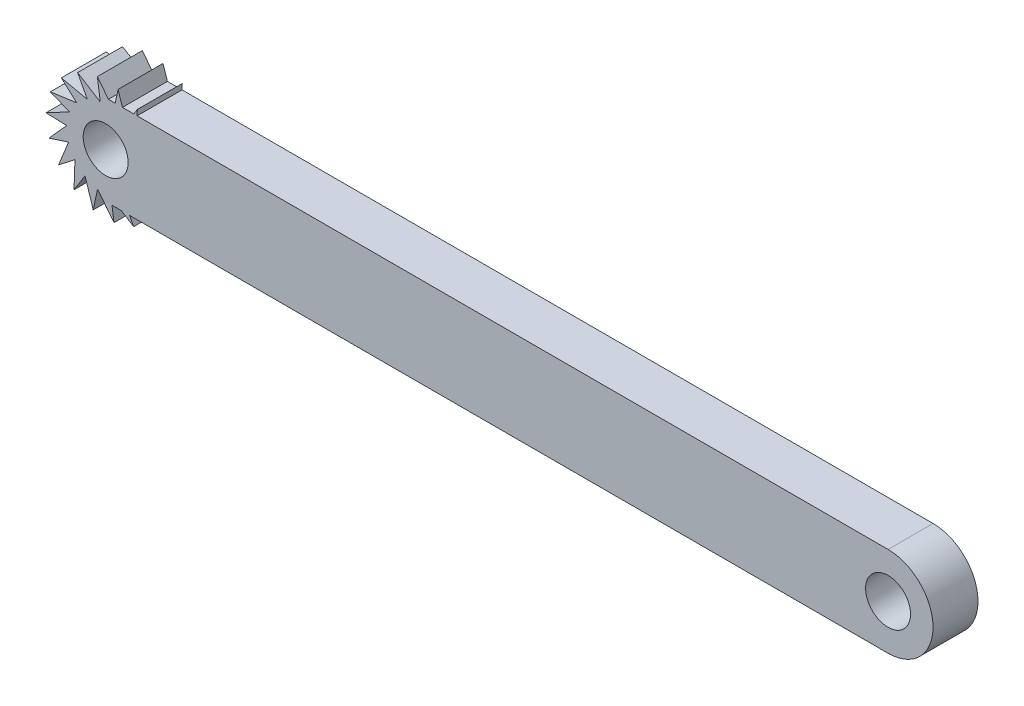
SolidWorks part; units mm, degrees
material "1060 Alloy"
ref_plane "Front Plane" through (0, 0, 0) normal (0, 0, 1) x (1, 0, 0)
ref_plane "Top Plane" through (0, 0, 0) normal (0, 1, 0) x (1, 0, 0)
ref_plane "Right Plane" through (0, 0, 0) normal (1, 0, 0) x (0, 0, -1)
sketch "Sketch1" plane through (0, 0, 0) normal (0, 0, 1) x (1, 0, 0)
  line L0 (-71.3706, 0) -> (276.6294, 0) construction
  line L1 (-71.3706, 20) -> (276.6294, 20)
  line L2 (-71.3706, -20) -> (276.6294, -20)
  arc A0 (-71.3706, 20) -> (-71.3706, -20) centre (-71.3706, 0) ccw
  arc A1 (276.6294, -20) -> (276.6294, 20) centre (276.6294, 0) ccw
  circle A2 centre (-71.3706, 0) radius 10
  circle A3 centre (276.6294, 0) radius 10
  point P3 (102.6294, 0)
extrude "Boss-Extrude1" add sketch "Sketch1" along normal blind 20
sketch "Sketch2" plane through (0, 0, 0) normal (0, 0, -1) x (-1, 0, 0)
  line L0 (71.3706, -20) -> (71.3706, -25)
  line L1 (62.5643, -17.9569) -> (58.8706, -21.6506)
  arc A0 (62.5643, -17.9569) -> (71.3706, -20) centre (71.3706, 0) ccw
  arc A1 (58.8706, -21.6506) -> (71.3706, -25) centre (71.3706, 0) ccw
  arc A2 (71.3706, -20) -> (71.3706, 20) centre (71.3706, 0) ccw construction
  dimension "D1" = 50
  dimension "D2" = 45
extrude "Boss-Extrude2" add sketch "Sketch2" along normal blind 20
ref_plane "Plane1" through (0, 0, 15) normal (0, 0, 1) x (1, 0, 0)
sketch "Sketch6" plane through (0, 0, 15) normal (0, 0, 1) x (1, 0, 0)
  line L0 (-65.8481, 25.9708) -> (-62.1857, 14.6962)
  line L1 (-67.766, 16.9513) -> (-65.8481, 25.9708)
  line L2 (-75.0637, 26.2934) -> (-67.766, 16.9513)
  line L3 (-62.1857, 14.6962) -> (-57.2986, 22.5158)
  line L4 (-57.2986, 22.5158) -> (-57.7133, 10.6685)
  line L5 (-57.7133, 10.6685) -> (-50.4464, 16.3451)
  line L6 (-50.4464, 16.3451) -> (-54.8881, 5.354)
  line L7 (-54.8881, 5.354) -> (-46.1179, 8.2028)
  line L8 (-46.1179, 8.2028) -> (-54.0509, -0.6062)
  line L9 (-54.0509, -0.6062) -> (-44.8353, -0.9288)
  line L10 (-44.8353, -0.9288) -> (-55.3027, -6.4933)
  line L11 (-55.3027, -6.4933) -> (-46.7532, -9.9483)
  line L12 (-46.7532, -9.9483) -> (-58.4926, -11.5972)
  line L13 (-58.4926, -11.5972) -> (-51.6404, -17.768)
  line L14 (-51.6404, -17.768) -> (-63.2357, -15.3024)
  line L15 (-63.2357, -15.3024) -> (-58.9073, -23.4446)
  line L16 (-58.9073, -23.4446) -> (-68.96, -17.1618)
  line L17 (-68.96, -17.1618) -> (-67.6774, -26.2934)
  line L18 (-67.6774, -26.2934) -> (-74.9751, -16.9513)
  line L19 (-74.9751, -16.9513) -> (-76.893, -25.9708)
  line L20 (-76.893, -25.9708) -> (-80.5554, -14.6962)
  line L21 (-80.5554, -14.6962) -> (-85.4425, -22.5158)
  line L22 (-85.4425, -22.5158) -> (-85.0278, -10.6685)
  line L23 (-85.0278, -10.6685) -> (-92.2947, -16.3451)
  line L24 (-92.2947, -16.3451) -> (-87.853, -5.354)
  line L25 (-87.853, -5.354) -> (-96.6232, -8.2028)
  line L26 (-96.6232, -8.2028) -> (-88.6902, 0.6062)
  line L27 (-88.6902, 0.6062) -> (-97.9058, 0.9288)
  line L28 (-97.9058, 0.9288) -> (-87.4384, 6.4933)
  line L29 (-87.4384, 6.4933) -> (-95.9879, 9.9483)
  line L30 (-95.9879, 9.9483) -> (-84.2485, 11.5972)
  line L31 (-84.2485, 11.5972) -> (-91.1008, 17.768)
  line L32 (-91.1008, 17.768) -> (-79.5054, 15.3024)
  line L33 (-79.5054, 15.3024) -> (-83.8339, 23.4446)
  line L34 (-83.8339, 23.4446) -> (-73.7811, 17.1618)
  line L35 (-73.7811, 17.1618) -> (-75.0637, 26.2934)
  circle A0 centre (-71.3706, 0) radius 26.5515 construction
  circle A1 centre (-71.3706, 0) radius 17.3303 construction
  circle A2 centre (-71.3706, 0) radius 10
  point P61 (-71.3706, 0)
  dimension "D1" = 50
  dimension "D2" = 18
extrude "Boss-Extrude3" add sketch "Sketch6" against normal blind 15 and the other way blind 10 contours L30 L31 L32 L33 L34 L35 L2 L1 L0 L3 L4 L5 L6 L7 L8 L9 L10 L11 L12 L13 L14 L15 L16 L17 L18 L19 L20 L21 L22 L23 L24 L25 L26 L27 L28 L29
sketch "Sketch8" plane through (0, 0, 0) normal (0, 0, -1) x (-1, 0, 0)
  line L36 (88.6902, 0.6062) -> (97.9058, 0.9288)
  line L37 (97.9058, 0.9288) -> (87.4384, 6.4933)
  line L38 (87.4384, 6.4933) -> (95.9879, 9.9483)
  line L39 (95.9879, 9.9483) -> (84.2485, 11.5972)
  line L40 (84.2485, 11.5972) -> (91.1008, 17.768)
  line L41 (91.1008, 17.768) -> (79.5054, 15.3024)
  line L42 (79.5054, 15.3024) -> (83.8339, 23.4446)
  line L43 (83.8339, 23.4446) -> (73.7811, 17.1618)
  line L44 (73.7811, 17.1618) -> (75.0637, 26.2934)
  line L45 (75.0637, 26.2934) -> (67.766, 16.9513)
  line L46 (67.766, 16.9513) -> (65.8481, 25.9708)
  line L47 (65.8481, 25.9708) -> (62.1857, 14.6962)
  line L48 (62.1857, 14.6962) -> (57.2986, 22.5158)
  line L49 (57.2986, 22.5158) -> (57.7133, 10.6685)
  line L50 (57.7133, 10.6685) -> (50.4464, 16.3451)
  line L51 (50.4464, 16.3451) -> (54.8881, 5.354)
  line L52 (54.8881, 5.354) -> (46.1179, 8.2028)
  line L53 (46.1179, 8.2028) -> (54.0509, -0.6062)
  line L54 (54.0509, -0.6062) -> (44.8353, -0.9288)
  line L55 (44.8353, -0.9288) -> (55.3027, -6.4933)
  line L56 (55.3027, -6.4933) -> (46.7532, -9.9483)
  line L57 (46.7532, -9.9483) -> (58.4926, -11.5972)
  line L58 (58.4926, -11.5972) -> (51.6404, -17.768)
  line L59 (51.6404, -17.768) -> (63.2357, -15.3024)
  line L60 (63.2357, -15.3024) -> (58.9073, -23.4446)
  line L61 (58.9073, -23.4446) -> (68.96, -17.1618)
  line L62 (68.96, -17.1618) -> (67.6774, -26.2934)
  line L63 (67.6774, -26.2934) -> (74.9751, -16.9513)
  line L64 (74.9751, -16.9513) -> (76.893, -25.9708)
  line L65 (76.893, -25.9708) -> (80.5554, -14.6962)
  line L66 (80.5554, -14.6962) -> (85.4425, -22.5158)
  line L67 (85.4425, -22.5158) -> (85.0278, -10.6685)
  line L68 (85.0278, -10.6685) -> (92.2947, -16.3451)
  line L69 (92.2947, -16.3451) -> (87.853, -5.354)
  line L70 (87.853, -5.354) -> (96.6232, -8.2028)
  line L71 (96.6232, -8.2028) -> (88.6902, 0.6062)
  line L72 (88.6902, 0.6062) -> (97.9058, 0.9288)
  line L73 (97.9058, 0.9288) -> (87.4384, 6.4933)
  line L74 (87.4384, 6.4933) -> (95.9879, 9.9483)
  line L75 (95.9879, 9.9483) -> (84.2485, 11.5972)
  line L76 (84.2485, 11.5972) -> (91.1008, 17.768)
  line L77 (91.1008, 17.768) -> (79.5054, 15.3024)
  line L78 (79.5054, 15.3024) -> (83.8339, 23.4446)
  line L79 (83.8339, 23.4446) -> (73.7811, 17.1618)
  line L80 (73.7811, 17.1618) -> (75.0637, 26.2934)
  line L81 (75.0637, 26.2934) -> (67.766, 16.9513)
  line L82 (67.766, 16.9513) -> (65.8481, 25.9708)
  line L83 (65.8481, 25.9708) -> (62.1857, 14.6962)
  line L84 (62.1857, 14.6962) -> (57.2986, 22.5158)
  line L85 (57.2986, 22.5158) -> (57.7133, 10.6685)
  line L86 (57.7133, 10.6685) -> (50.4464, 16.3451)
  line L87 (50.4464, 16.3451) -> (54.8881, 5.354)
  line L88 (54.8881, 5.354) -> (46.1179, 8.2028)
  line L89 (46.1179, 8.2028) -> (54.0509, -0.6062)
  line L90 (54.0509, -0.6062) -> (44.8353, -0.9288)
  line L91 (44.8353, -0.9288) -> (55.3027, -6.4933)
  line L92 (55.3027, -6.4933) -> (46.7532, -9.9483)
  line L93 (46.7532, -9.9483) -> (58.4926, -11.5972)
  line L94 (58.4926, -11.5972) -> (51.6404, -17.768)
  line L95 (51.6404, -17.768) -> (63.2357, -15.3024)
  line L96 (63.2357, -15.3024) -> (58.9073, -23.4446)
  line L97 (58.9073, -23.4446) -> (68.96, -17.1618)
  line L98 (68.96, -17.1618) -> (67.6774, -26.2934)
  line L99 (67.6774, -26.2934) -> (74.9751, -16.9513)
  line L100 (74.9751, -16.9513) -> (76.893, -25.9708)
  line L101 (76.893, -25.9708) -> (80.5554, -14.6962)
  line L102 (80.5554, -14.6962) -> (85.4425, -22.5158)
  line L103 (85.4425, -22.5158) -> (85.0278, -10.6685)
  line L104 (85.0278, -10.6685) -> (92.2947, -16.3451)
  line L105 (92.2947, -16.3451) -> (87.853, -5.354)
  line L106 (87.853, -5.354) -> (96.6232, -8.2028)
  line L107 (96.6232, -8.2028) -> (88.6902, 0.6062)
  circle A0 centre (-71.3706, 0) radius 26.5515
  dimension "D1" = 0
sketch "Sketch10" plane through (0, 0, 20) normal (0, 0, 1) x (1, 0, 0)
  line L2 (-77.0194, 19.1857) -> (-73.7811, 17.1618)
  line L3 (-73.7811, 17.1618) -> (-74.1524, 19.8056)
  line L4 (-77.0194, 19.1857) -> (-73.7811, 17.1618)
  line L5 (-73.7811, 17.1618) -> (-74.1524, 19.8056)
  arc A1 (-74.1524, 19.8056) -> (-77.0194, 19.1857) centre (-71.3706, 0) ccw
  arc A2 (-74.1524, 19.8056) -> (-77.0194, 19.1857) centre (-71.3706, 0) ccw
  dimension "D1" = 0
extrude "Cut-Extrude1" cut sketch "Sketch10" against normal up to surface (20 mm away) up to face at (-61.0679, 1.6244, 0)
ref_axis "Axis1" through (-71.3706, 0, 20) along (0, 0, -1)
pattern_circular "CirPattern1" count 18 over 360 about axis through (-71.3706, 0, 20) along (0, 0, -1) skipping 1, 2, 3, 4, 5, 6, 7, 8, 9 of "Cut-Extrude1"
sketch "Sketch11" plane through (0, 0, 25) normal (0, 0, 1) x (1, 0, 0)
  circle A1 centre (-71.3706, 0) radius 10
  circle A2 centre (-71.3706, 0) radius 10
  dimension "D1" = 0
extrude "Cut-Extrude3" cut sketch "Sketch11" against normal blind 33
sketch "Sketch12" plane through (0, 0, 25) normal (0, 0, 1) x (1, 0, 0)
  line L36 (-97.9058, 0.9288) -> (-88.6902, 0.6062)
  line L37 (-87.4384, 6.4933) -> (-97.9058, 0.9288)
  line L38 (-95.9879, 9.9483) -> (-87.4384, 6.4933)
  line L39 (-84.2485, 11.5972) -> (-95.9879, 9.9483)
  line L40 (-91.1008, 17.768) -> (-84.2485, 11.5972)
  line L41 (-79.5054, 15.3024) -> (-91.1008, 17.768)
  line L42 (-83.8339, 23.4446) -> (-79.5054, 15.3024)
  line L43 (-73.7811, 17.1618) -> (-83.8339, 23.4446)
  line L44 (-75.0637, 26.2934) -> (-73.7811, 17.1618)
  line L45 (-67.766, 16.9513) -> (-75.0637, 26.2934)
  line L46 (-65.8481, 25.9708) -> (-67.766, 16.9513)
  line L47 (-62.1857, 14.6962) -> (-65.8481, 25.9708)
  line L48 (-57.2986, 22.5158) -> (-62.1857, 14.6962)
  line L49 (-57.7133, 10.6685) -> (-57.2986, 22.5158)
  line L50 (-50.4464, 16.3451) -> (-57.7133, 10.6685)
  line L51 (-54.8881, 5.354) -> (-50.4464, 16.3451)
  line L52 (-46.1179, 8.2028) -> (-54.8881, 5.354)
  line L53 (-54.0509, -0.6062) -> (-46.1179, 8.2028)
  line L54 (-44.8353, -0.9288) -> (-54.0509, -0.6062)
  line L55 (-55.3027, -6.4933) -> (-44.8353, -0.9288)
  line L56 (-46.7532, -9.9483) -> (-55.3027, -6.4933)
  line L57 (-58.4926, -11.5972) -> (-46.7532, -9.9483)
  line L58 (-51.6404, -17.768) -> (-58.4926, -11.5972)
  line L59 (-63.2357, -15.3024) -> (-51.6404, -17.768)
  line L60 (-58.9073, -23.4446) -> (-63.2357, -15.3024)
  line L61 (-68.96, -17.1618) -> (-58.9073, -23.4446)
  line L62 (-67.6774, -26.2934) -> (-68.96, -17.1618)
  line L63 (-74.9751, -16.9513) -> (-67.6774, -26.2934)
  line L64 (-76.893, -25.9708) -> (-74.9751, -16.9513)
  line L65 (-80.5554, -14.6962) -> (-76.893, -25.9708)
  line L66 (-85.4425, -22.5158) -> (-80.5554, -14.6962)
  line L67 (-85.0278, -10.6685) -> (-85.4425, -22.5158)
  line L68 (-92.2947, -16.3451) -> (-85.0278, -10.6685)
  line L69 (-87.853, -5.354) -> (-92.2947, -16.3451)
  line L70 (-96.6232, -8.2028) -> (-87.853, -5.354)
  line L71 (-88.6902, 0.6062) -> (-96.6232, -8.2028)
  line L72 (-97.9058, 0.9288) -> (-88.6902, 0.6062)
  line L73 (-87.4384, 6.4933) -> (-97.9058, 0.9288)
  line L74 (-95.9879, 9.9483) -> (-87.4384, 6.4933)
  line L75 (-84.2485, 11.5972) -> (-95.9879, 9.9483)
  line L76 (-91.1008, 17.768) -> (-84.2485, 11.5972)
  line L77 (-79.5054, 15.3024) -> (-91.1008, 17.768)
  line L78 (-83.8339, 23.4446) -> (-79.5054, 15.3024)
  line L79 (-73.7811, 17.1618) -> (-83.8339, 23.4446)
  line L80 (-75.0637, 26.2934) -> (-73.7811, 17.1618)
  line L81 (-67.766, 16.9513) -> (-75.0637, 26.2934)
  line L82 (-65.8481, 25.9708) -> (-67.766, 16.9513)
  line L83 (-62.1857, 14.6962) -> (-65.8481, 25.9708)
  line L84 (-57.2986, 22.5158) -> (-62.1857, 14.6962)
  line L85 (-57.7133, 10.6685) -> (-57.2986, 22.5158)
  line L86 (-50.4464, 16.3451) -> (-57.7133, 10.6685)
  line L87 (-54.8881, 5.354) -> (-50.4464, 16.3451)
  line L88 (-46.1179, 8.2028) -> (-54.8881, 5.354)
  line L89 (-54.0509, -0.6062) -> (-46.1179, 8.2028)
  line L90 (-44.8353, -0.9288) -> (-54.0509, -0.6062)
  line L91 (-55.3027, -6.4933) -> (-44.8353, -0.9288)
  line L92 (-46.7532, -9.9483) -> (-55.3027, -6.4933)
  line L93 (-58.4926, -11.5972) -> (-46.7532, -9.9483)
  line L94 (-51.6404, -17.768) -> (-58.4926, -11.5972)
  line L95 (-63.2357, -15.3024) -> (-51.6404, -17.768)
  line L96 (-58.9073, -23.4446) -> (-63.2357, -15.3024)
  line L97 (-68.96, -17.1618) -> (-58.9073, -23.4446)
  line L98 (-67.6774, -26.2934) -> (-68.96, -17.1618)
  line L99 (-74.9751, -16.9513) -> (-67.6774, -26.2934)
  line L100 (-76.893, -25.9708) -> (-74.9751, -16.9513)
  line L101 (-80.5554, -14.6962) -> (-76.893, -25.9708)
  line L102 (-85.4425, -22.5158) -> (-80.5554, -14.6962)
  line L103 (-85.0278, -10.6685) -> (-85.4425, -22.5158)
  line L104 (-92.2947, -16.3451) -> (-85.0278, -10.6685)
  line L105 (-87.853, -5.354) -> (-92.2947, -16.3451)
  line L106 (-96.6232, -8.2028) -> (-87.853, -5.354)
  line L107 (-88.6902, 0.6062) -> (-96.6232, -8.2028)
  circle A1 centre (-71.3706, 0) radius 10
  circle A2 centre (-71.3706, 0) radius 10
  dimension "D1" = 0
  dimension "D2" = 0
extrude "Cut-Extrude4" cut sketch "Sketch12" against normal blind 5
ref_plane "Plane2" through (40, 0, 0) normal (1, 0, 0) x (0, 0, -1)
sketch "Sketch13" plane through (40, 0, 0) normal (1, 0, 0) x (0, 0, -1)
  arc A0 (63, 63) -> (63, -63) centre (63, 0) ccw
